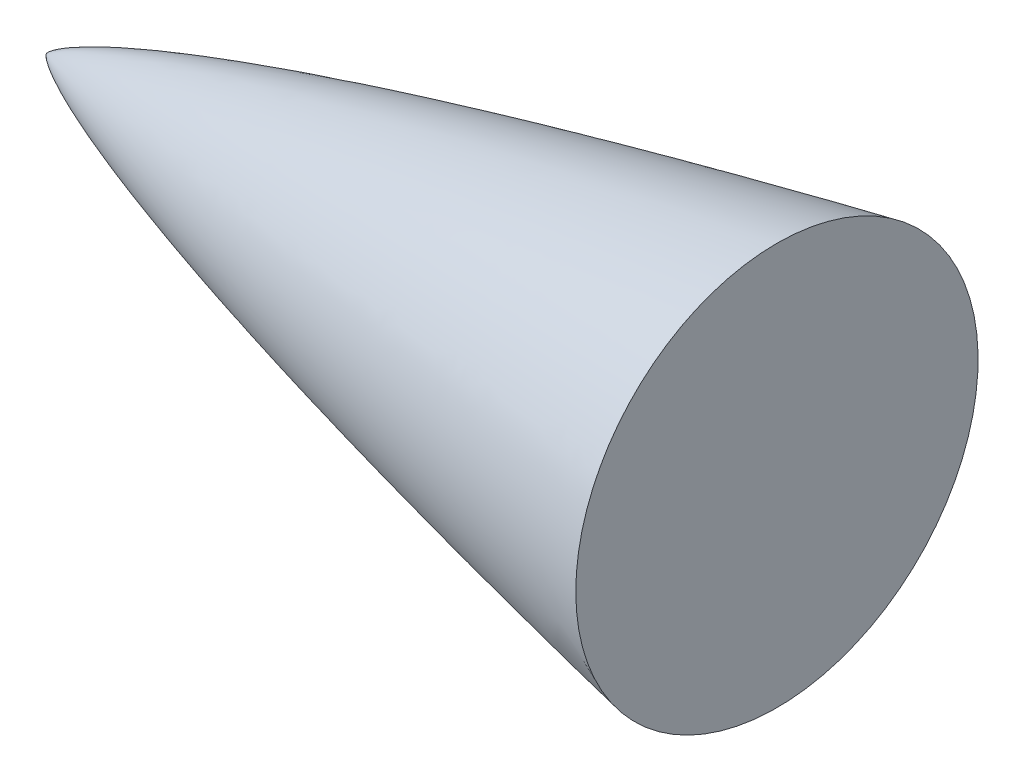
SolidWorks part; units mm, degrees
material "1060 Alloy"
ref_plane "Front Plane" through (0, 0, 0) normal (0, 0, 1) x (1, 0, 0)
ref_plane "Top Plane" through (0, 0, 0) normal (0, 1, 0) x (1, 0, 0)
ref_plane "Right Plane" through (0, 0, 0) normal (1, 0, 0) x (0, 0, -1)
sketch "Sketch1" plane through (0, 0, 0) normal (0, 0, 1) x (1, 0, 0)
  line L0 (0, 0) -> (44.45, 0)
  line L1 (44.45, 0) -> (44.45, 12.2404)
  spline S0 degree 4 poles (0, 0) (0.003, 0.0098) (0.0106, 0.0263) (0.0259, 0.0477) (0.0496, 0.0773) (0.0811, 0.1115) (0.1284, 0.1575) (0.2052, 0.2238) (0.3322, 0.3214) (0.5446, 0.4658) (0.9016, 0.6802) (1.5114, 1.0017) (2.4628, 1.4428) (4.093, 2.1112) (6.3816, 2.9359) (9.2264, 3.8553) (12.4937, 4.8221) (15.8352, 5.7433) (19.1577, 6.6111) (22.5404, 7.451) (25.8486, 8.2426) (29.2981, 9.0336) (32.5312, 9.7563) (36.1346, 10.5306) (39.1375, 11.1649) (42.7985, 11.9108) (44.8638, 12.3243) (46.8343, 12.7126) (48.2067, 12.9815) (48.5075, 13.0385) (48.933, 13.1217) knots 0 0 0 0 0 0.000801 0.001434 0.00205 0.002997 0.004453 0.00663 0.010024 0.015611 0.024646 0.039425 0.064225 0.09821 0.163174 0.231144 0.299114 0.367084 0.435053 0.503023 0.570993 0.638963 0.706933 0.774903 0.842873 0.910843 0.955421 0.977711 1 1 1 1 1 construction
  spline S1 degree 4 poles (0, 0) (0.003, 0.0098) (0.0106, 0.0263) (0.0259, 0.0477) (0.0496, 0.0773) (0.0811, 0.1115) (0.1284, 0.1575) (0.2052, 0.2238) (0.3322, 0.3214) (0.5446, 0.4658) (0.9016, 0.6802) (1.5114, 1.0017) (2.4628, 1.4428) (4.093, 2.1112) (6.3816, 2.9359) (9.2264, 3.8553) (12.4937, 4.8221) (15.8352, 5.7433) (19.1577, 6.6111) (22.5404, 7.451) (25.8486, 8.2426) (29.2981, 9.0336) (32.5312, 9.7563) (36.1346, 10.5306) (39.1375, 11.1649) (42.1417, 11.7769) (43.6788, 12.0864) (44.45, 12.2404) knots 0 0 0 0 0 0.000801 0.001434 0.00205 0.002997 0.004453 0.00663 0.010024 0.015611 0.024646 0.039425 0.064225 0.09821 0.163174 0.231144 0.299114 0.367084 0.435053 0.503023 0.570993 0.638963 0.706933 0.774903 0.842873 0.910843 0.910843 0.910843 0.910843 0.910843
  dimension "D1" = 44.45
revolve "Revolve1" add sketch "Sketch1" angle 360 about L0
ref_axis "Axis1" through (46.6725, 0, 0) along (-1, 0, 0)
